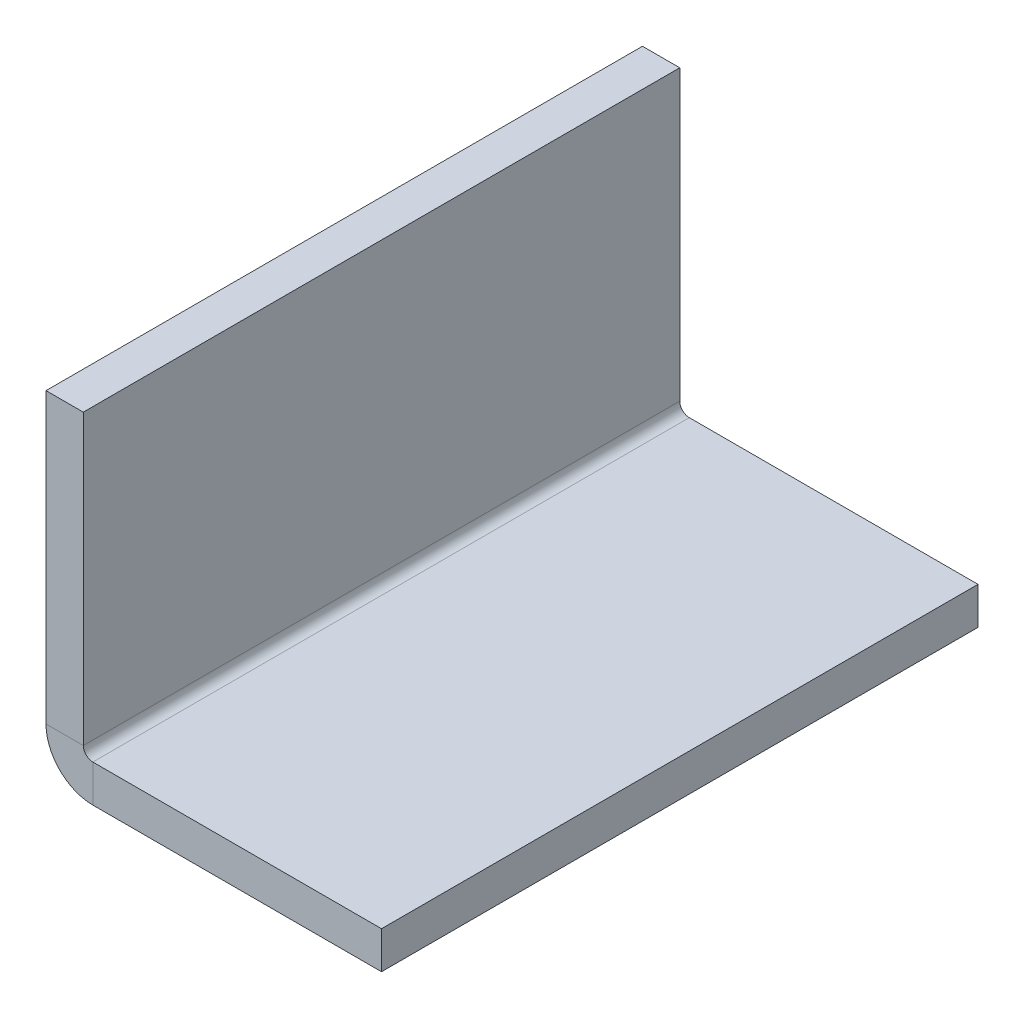
SolidWorks part; units mm, degrees
note: The reader was unsure of these and kept them because the rebuilt part matched: bend radius of "BaseBend1".
material "6061 Alloy"
ref_plane "Front Plane" through (0, 0, 0) normal (0, 0, 1) x (1, 0, 0)
ref_plane "Top Plane" through (0, 0, 0) normal (0, 1, 0) x (1, 0, 0)
ref_plane "Right Plane" through (0, 0, 0) normal (1, 0, 0) x (0, 0, -1)
sketch "Sketch1" plane through (0, 0, 0) normal (0, 0, 1) x (1, 0, 0)
  line L0 (0, 25.4) -> (0, 0)
  line L1 (0, 0) -> (25.4, 0)
  dimension "D1" = 25.4
base flange "Base-Flange1" sketch "Sketch1" end condition mid plane depth 50.8 reverse direction no thickness 3.175 reverse thickness direction no bend radius 0.8128
bend "BaseBend1" bend radius 0.8128 bend angle 90 parameters "D5"=1
sketch "Bend-Lines1" [suppressed] plane through (0, 0, 0) normal (0, 1, 0) x (1, 0, 0)
sketch "Bounding-Box1" [suppressed] plane through (0, 0, 0) normal (0, 1, 0) x (1, 0, 0)
sheet metal parameters "Sheet-Metal1" thickness 3.175 parameters "D1"=0.8128
flat pattern "Flat-Pattern1" [suppressed]
sketch "Bend-Lines2" plane through (0, 0, 0) normal (0, 1, 0) x (1, 0, 0)
  line L0 (-1.0724, -25.4) -> (-1.0724, 25.4) construction
  line L1 (-1.0724, -25.4) -> (-1.0724, 25.4) construction
sketch3d "Bounding-Box2" [suppressed]
  line L0 (25.4, 0, 0) -> (-27.5448, 0, 0) construction
  line L1 (25.4, 50.8, 0) -> (-27.5448, 50.8, 0) construction
  line L2 (25.4, 0, 0) -> (25.4, 50.8, 0) construction
  line L3 (-27.5448, 0, 0) -> (-27.5448, 50.8, 0) construction
bend of the flat pattern "Flatten-<BaseBend1>1"
